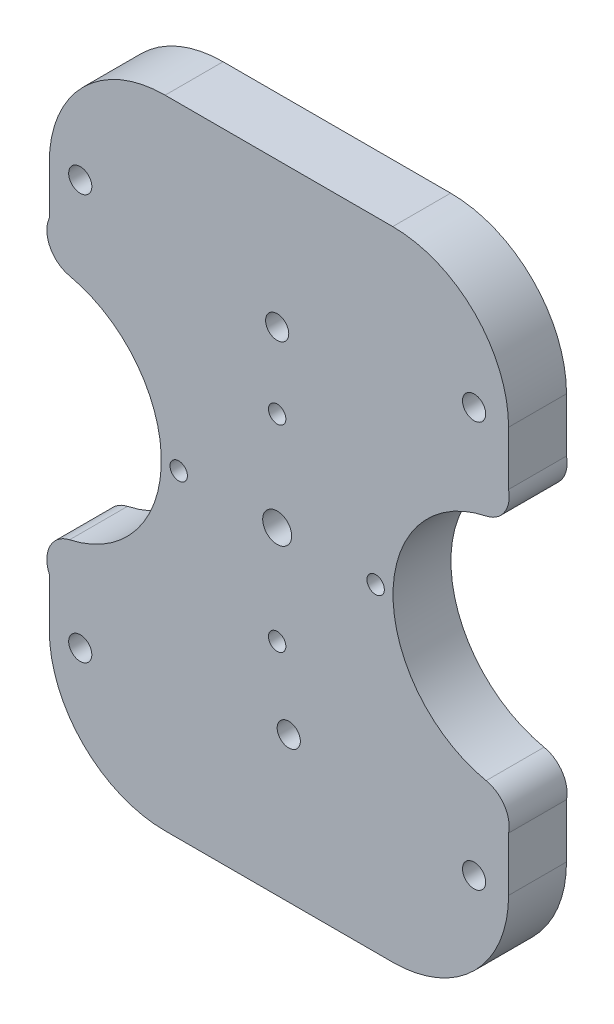
SolidWorks part; units mm, degrees
ref_plane "Front Plane" through (0, 0, 0) normal (0, 0, 1) x (1, 0, 0)
ref_plane "Top Plane" through (0, 0, 0) normal (0, 1, 0) x (1, 0, 0)
ref_plane "Right Plane" through (0, 0, 0) normal (1, 0, 0) x (0, 0, -1)
sketch "Sketch1" plane through (0, 0, 0) normal (0, 0, 1) x (1, 0, 0)
  line L0 (0, 57.5241) -> (0, -57.5241) construction
  line L1 (-61.4517, 0) -> (61.4517, 0) construction
  circle A0 centre (0, 0) radius 47.5
  circle A1 centre (0, 0) radius 2.5
  circle A2 centre (0, 17) radius 1.5
  circle A3 centre (17, 0) radius 1.5
  circle A4 centre (0, -17) radius 1.5
  circle A5 centre (-17, 0) radius 1.5
  point P15 (-4.7966, 0.2687)
  point P16 (-8, 57.5241)
  point P18 (-8, -57.5241)
  point P19 (-61.4517, -8)
  point P20 (61.4517, -8)
  point P21 (8, 57.5241)
  point P23 (8, -57.5241)
  point P24 (-61.4517, 8)
  point P25 (61.4517, 8)
  dimension "D1" = 95
  dimension "D2" = 3
  dimension "D3" = 5
  dimension "D4" = 17
  dimension "D5" = 17
  dimension "D6" = 17
  dimension "D7" = 17
extrude "Boss-Extrude1" add sketch "Sketch1" along normal blind 10
sketch "Sketch7" plane through (0, 0, 0) normal (0, 0, -1) x (-1, 0, 0)
  line L0 (-47.5, 0) -> (47.5, 0) construction
  circle A0 centre (0, 0) radius 47.5 construction
  point P5 (0, 0)
  line B0 (-45.9933, 0) -> (45.9933, 0) construction
  line B1 (-39.9533, 55) -> (39.3416, 55)
  line B2 (-39.9533, 55) -> (-39.9533, 25)
  line B3 (-39.9533, 25) -> (39.3416, 25)
  line B4 (39.3416, 55) -> (39.3416, 25)
  line B5 (-39.9533, 55) -> (39.3416, 25) construction
  line B6 (-39.9533, 25) -> (39.3416, 55) construction
  line B7 (-39.9533, -25) -> (39.3416, -55) construction
  line B8 (-39.9533, -55) -> (39.3416, -25) construction
  line B9 (39.3416, -55) -> (39.3416, -25)
  line B10 (-39.9533, -25) -> (39.3416, -25)
  line B11 (-39.9533, -55) -> (-39.9533, -25)
  line B12 (-39.9533, -55) -> (39.3416, -55)
sketch_block_instance "Block1-1"
sketch_block "Block1" parameters "D1"=30, "D2"=40
extrude "Boss-Extrude3" add sketch "Sketch7" against normal blind 10
sketch "Sketch3" plane through (0, 0, 10) normal (0, 0, 1) x (1, 0, 0)
  line L0 (0, 34.0183) -> (0, -25.2417) construction
  line L1 (-47.5, 0) -> (47.5, 0) construction
  circle A0 centre (-34, 35) radius 2
  circle A1 centre (34, 35) radius 2
  circle A2 centre (0, 0) radius 47.5 construction
  dimension "D1" = 4
  dimension "D2" = 4
  dimension "D5" = 35
  dimension "D3" = 34
  dimension "D4" = 34
extrude "Cut-Extrude1" cut sketch "Sketch3" against normal blind 10
mirror "Mirror1" about plane through (0, 0, 0) normal (0, 1, 0) of "Cut-Extrude1"
sketch "Sketch4" plane through (0, 0, 10) normal (0, 0, 1) x (1, 0, 0)
  line L0 (0, 47.5) -> (0, -47.5) construction
  line L1 (-20, 20) -> (-20, -47.5) construction
  line L2 (20, 0) -> (20, -47.5) construction
  line L3 (-47.5, 0) -> (47.5, 0) construction
  line L4 (-47.5, -20) -> (47.5, -20) construction
  line L5 (-68.0258, 20) -> (69.2713, 20) construction
  line L6 (20, 47.5) -> (20, -47.5) construction
  line L7 (-20, 47.5) -> (-20, -47.5) construction
  circle A0 centre (0, 0) radius 47.5 construction
  arc A1 (-43.0842, 20) -> (-43.0842, -20) centre (0, 0) ccw
  arc A2 (-43.0842, 20) -> (-43.0842, -20) centre (-40.206, 0) cw
  arc A3 (43.0842, 20) -> (43.0842, -20) centre (0, 0) cw
  arc A4 (43.0842, 20) -> (43.0842, -20) centre (40.206, 0) ccw
  point P13 (-47.5, 20)
  point P14 (47.5, 20)
  dimension "D1" = 20
  dimension "D3" = 20
  dimension "D4" = 20
  dimension "D2" = 20
extrude "Cut-Extrude2" cut sketch "Sketch4" against normal blind 10
fillet "Fillet2" radius 5 4 edges at (43.0842, 20, 5) (43.0842, -20, 5) (-43.0842, -20, 5) (-43.0842, 20, 5)
fillet "Fillet3" radius 20 4 edges at (-39.3416, -55, 5) (39.9533, -55, 5) (39.9533, 55, 5) (-39.3416, 55, 5)
sketch "Sketch8" plane through (0, 0, 0) normal (0, 0, -1) x (-1, 0, 0)
  circle A0 centre (0, 0) radius 30 construction
  circle A1 centre (0, 30) radius 2
  circle A2 centre (-2, -29.9333) radius 2
  dimension "D1" = 60
  dimension "D2" = 4
  dimension "D3" = 4
extrude "Cut-Extrude3" cut sketch "Sketch8" against normal blind 20
